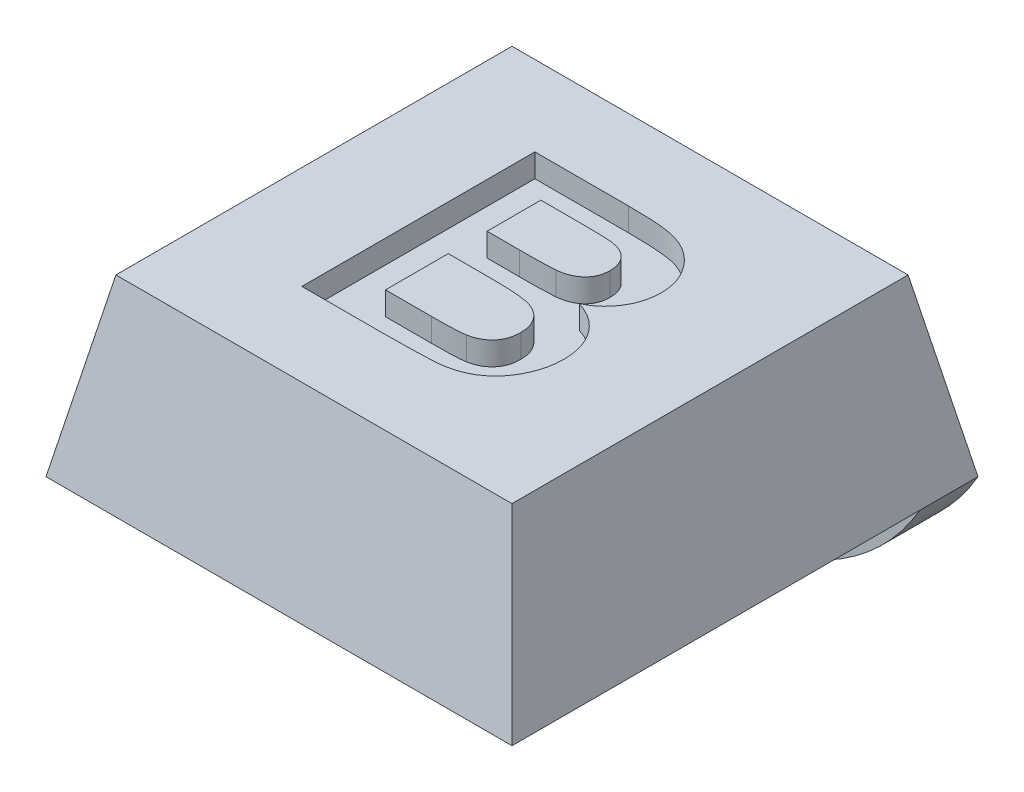
SolidWorks part; units mm, degrees
ref_plane "Front Plane" through (0, 0, 0) normal (0, 0, 1) x (1, 0, 0)
ref_plane "Top Plane" through (0, 0, 0) normal (0, 1, 0) x (1, 0, 0)
ref_plane "Right Plane" through (0, 0, 0) normal (1, 0, 0) x (0, 0, -1)
sketch "Sketch1" plane through (0, 0, 0) normal (0, 1, 0) x (1, 0, 0)
  line L1 (0, 0) -> (8, 0)
  line L2 (0, 0) -> (0, 8)
  line L3 (0, 8) -> (8, 8)
  line L4 (8, 0) -> (8, 8)
  dimension "D1" = 8
  dimension "D2" = 8
extrude "Boss-Extrude1" add sketch "Sketch1" along normal blind 3
sketch "Sketch2" plane through (0, 0, 0) normal (0, 0, 1) x (1, 0, 0)
  line L0 (0, 0) -> (0.6, 3)
  line L1 (0, 3) -> (8, 3) construction
  line L2 (0.6, 3) -> (0, 3)
  line L3 (0, 3) -> (0, 0)
  line L4 (8, 0) -> (7.4, 3)
  line L5 (7.4, 3) -> (8, 3)
  line L6 (8, 3) -> (8, 0)
  dimension "D1" = 0.6
  dimension "D2" = 0.6
extrude "Cut-Extrude1" cut sketch "Sketch2" against normal through all both and the other way through all
sketch "Sketch3" plane through (0, 0, 0) normal (1, 0, 0) x (0, 0, -1)
  line L0 (0, 0) -> (0.6, 3)
  line L1 (8, 3) -> (0, 3) construction
  line L2 (0.6, 3) -> (0, 3)
  line L3 (0, 3) -> (0, 0)
  line L4 (8, 3) -> (7.4, 3)
  line L5 (7.4, 3) -> (8, 0)
  line L6 (8, 3) -> (8, 0)
  dimension "D1" = 0.6
  dimension "D2" = 0.6
extrude "Cut-Extrude2" cut sketch "Sketch3" along normal blind 11
sketch "Sketch4" plane through (0, 0, 0) normal (0, -1, 0) x (1, 0, 0)
  line L0 (8, 0) -> (8, -8) construction
  line L3 (0, 0) -> (8, 0) construction
  circle A0 centre (4, -3.75) radius 1.8
  dimension "D1" = 3.6
  dimension "D2" = 4
  dimension "D3" = 3.75
extrude "Cut-Extrude3" cut sketch "Sketch4" against normal blind 0.8
sketch "Sketch5" plane through (0, 0, 0) normal (0, -1, 0) x (1, 0, 0)
  line L0 (8, 0) -> (8, -8) construction
  line L1 (0, -8) -> (8, -8)
  line L2 (0, -8) -> (0, -7)
  line L3 (0, -7) -> (8, -7)
  line L4 (8, -8) -> (8, -7)
  dimension "D1" = 1
extrude "Boss-Extrude2" add sketch "Sketch5" along normal blind 2
fillet "Fillet1" radius 4 2 edges at (8, -2, -7.5) (0, -2, -7.5)
sketch "Sketch6" plane through (0, 3, 0) normal (0, 1, 0) x (1, 0, 0)
  text T0 "B" font "Arial" height 4
extrude "Cut-Extrude4" cut sketch "Sketch6" against normal blind 0.4
